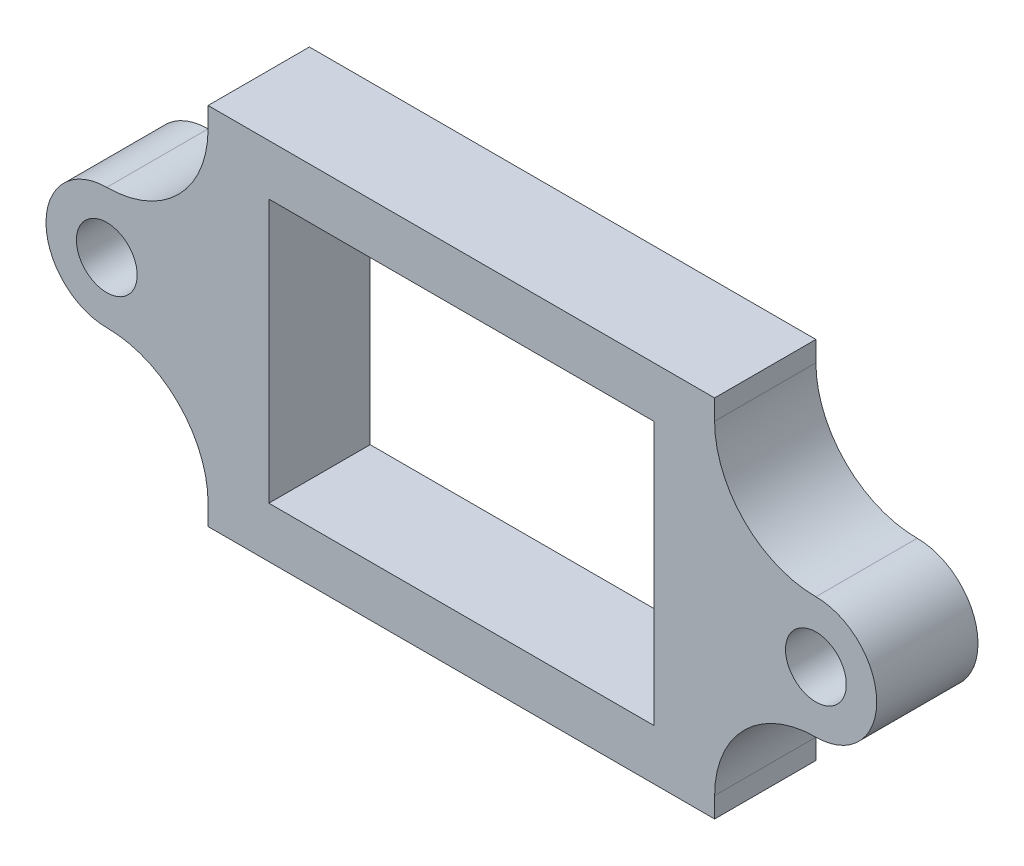
SolidWorks part; units mm, degrees
ref_plane "Front Plane" through (0, 0, 0) normal (0, 0, 1) x (1, 0, 0)
ref_plane "Top Plane" through (0, 0, 0) normal (0, 1, 0) x (1, 0, 0)
ref_plane "Right Plane" through (0, 0, 0) normal (1, 0, 0) x (0, 0, -1)
sketch "Sketch1" plane through (0, 0, 0) normal (0, 0, 1) x (1, 0, 0)
  line L1 (-12.5, -9) -> (12.5, -9)
  line L2 (-12.5, -9) -> (-12.5, 9)
  line L3 (-12.5, 9) -> (12.5, 9)
  line L4 (12.5, -9) -> (12.5, 9)
  line L5 (-12.5, -9) -> (12.5, 9) construction
  line L6 (-12.5, 9) -> (12.5, -9) construction
  line L7 (-9.5, -6.5) -> (9.5, -6.5)
  line L8 (-9.5, -6.5) -> (-9.5, 6.5)
  line L9 (-9.5, 6.5) -> (9.5, 6.5)
  line L10 (9.5, -6.5) -> (9.5, 6.5)
  line L11 (-9.5, -6.5) -> (9.5, 6.5) construction
  line L12 (-9.5, 6.5) -> (9.5, -6.5) construction
  point P0 (0, 0)
  point P6 (0, 0)
  dimension "D1" = 25
  dimension "D2" = 18
  dimension "D3" = 19
  dimension "D4" = 13
extrude "Boss-Extrude1" add sketch "Sketch1" along normal blind 5
sketch "Sketch2" plane through (0, 0, 0) normal (0, 0, -1) x (-1, 0, 0)
  line L0 (-12.5, -9) -> (-12.5, 9) construction
  line L1 (-12.5, 9) -> (12.5, 9) construction
  line L2 (-17.5, 3) -> (-12.5, 3)
  line L3 (-12.5, 3) -> (-12.5, -3)
  line L4 (-12.5, -3) -> (-17.5, -3)
  line L5 (0, 0) -> (0, 4.2309) construction
  line L6 (17.5, 3) -> (12.5, 3)
  line L7 (12.5, 3) -> (12.5, -3)
  line L8 (12.5, -3) -> (17.5, -3)
  circle A0 centre (-17.5, 0) radius 1.5
  arc A1 (-17.5, 3) -> (-17.5, -3) centre (-17.5, 0) ccw
  circle A2 centre (17.5, 0) radius 1.5
  arc A3 (17.5, 3) -> (17.5, -3) centre (17.5, 0) cw
  dimension "D1" = 5
  dimension "D2" = 3
  dimension "D3" = 9
  dimension "D4" = 6
extrude "Boss-Extrude2" add sketch "Sketch2" against normal blind 5
fillet "Fillet1" radius 5 4 edges at (12.5, -3, 2.5) (-12.5, -3, 2.5) (-12.5, 3, 2.5) (12.5, 3, 2.5)
